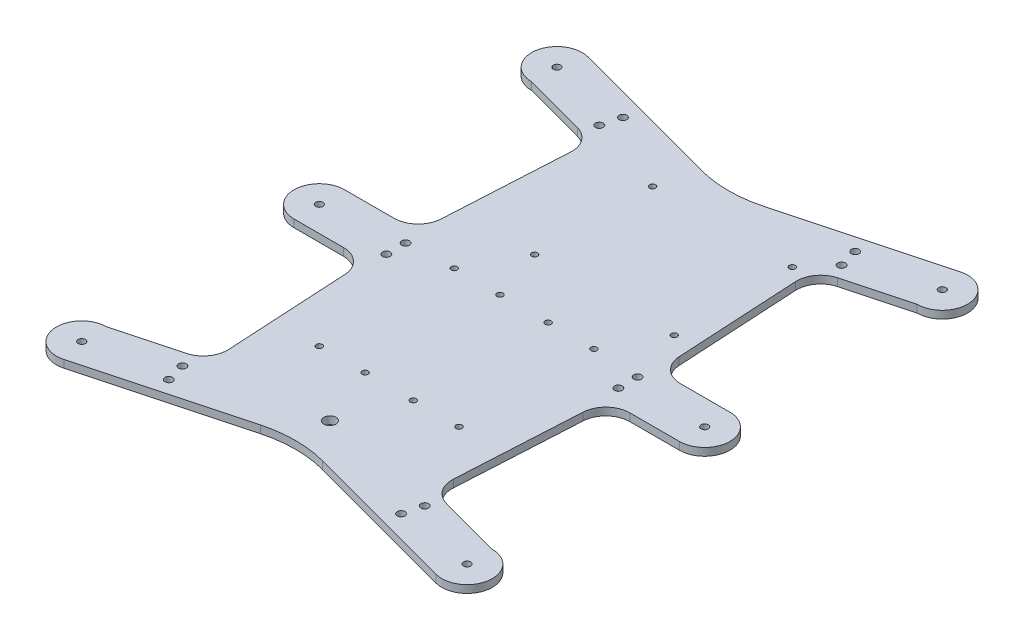
SolidWorks part; units mm, degrees
ref_plane "Front Plane" through (0, 0, 0) normal (0, 0, 1) x (1, 0, 0)
ref_plane "Top Plane" through (0, 0, 0) normal (0, 1, 0) x (1, 0, 0)
ref_plane "Right Plane" through (0, 0, 0) normal (1, 0, 0) x (0, 0, -1)
sketch "Sketch1" plane through (0, 0, 0) normal (0, 1, 0) x (1, 0, 0)
  line L0 (0, 32.1883) -> (0, -21.4181) construction
  line L1 (0, 0) -> (27.1703, 0) construction
  line L2 (-80, 10.5) -> (-50, 10.5)
  line L3 (-50, 10.5) -> (-46.1926, 79.0959)
  line L4 (-46.1926, 79.0959) -> (-80, 88.1546)
  line L5 (-77.2824, 108.7968) -> (0, 88.0891)
  line L6 (77.2824, 108.7968) -> (0, 88.0891)
  line L7 (46.1926, 79.0959) -> (80, 88.1546)
  line L8 (50, 10.5) -> (46.1926, 79.0959)
  line L9 (80, 10.5) -> (50, 10.5)
  line L10 (80, -10.5) -> (50, -10.5)
  line L11 (50, -10.5) -> (46.1926, -79.0959)
  line L12 (46.1926, -79.0959) -> (80, -88.1546)
  line L13 (77.2824, -108.7968) -> (0, -88.0891)
  line L14 (-77.2824, -108.7968) -> (0, -88.0891)
  line L15 (-46.1926, -79.0959) -> (-80, -88.1546)
  line L16 (-50, -10.5) -> (-46.1926, -79.0959)
  line L17 (-80, -10.5) -> (-50, -10.5)
  arc A0 (-80, 10.5) -> (-80, -10.5) centre (-80, 0) ccw
  arc A1 (-77.2824, 108.7968) -> (-80, 88.1546) centre (-80, 98.6546) ccw
  circle A2 centre (-80, 98.6546) radius 1.5
  circle A3 centre (-80, 0) radius 1.5
  circle A4 centre (80, 0) radius 1.5
  circle A5 centre (80, 98.6546) radius 1.5
  arc A6 (77.2824, 108.7968) -> (80, 88.1546) centre (80, 98.6546) cw
  arc A7 (80, 10.5) -> (80, -10.5) centre (80, 0) cw
  arc A8 (77.2824, -108.7968) -> (80, -88.1546) centre (80, -98.6546) ccw
  circle A9 centre (80, -98.6546) radius 1.5
  circle A10 centre (-80, -98.6546) radius 1.5
  arc A11 (-77.2824, -108.7968) -> (-80, -88.1546) centre (-80, -98.6546) cw
  circle A12 centre (-48.175, 4) radius 1.6 construction
  circle A13 centre (-50.2947, 86.554) radius 1.6 construction
  circle A14 centre (-48.2241, 94.2814) radius 1.6 construction
  circle A15 centre (-48.175, 4) radius 1.6
  circle A16 centre (-50.2947, 86.554) radius 1.6
  circle A17 centre (-48.2241, 94.2814) radius 1.6
  circle A18 centre (-50.2947, -86.554) radius 1.6
  circle A19 centre (-48.2241, -94.2814) radius 1.6
  circle A20 centre (-48.175, -4) radius 1.6
  circle A21 centre (48.2241, -94.2814) radius 1.6
  circle A22 centre (50.2947, -86.554) radius 1.6
  circle A23 centre (48.175, -4) radius 1.6
  circle A24 centre (48.175, 4) radius 1.6
  circle A25 centre (48.2241, 94.2814) radius 1.6
  circle A26 centre (50.2947, 86.554) radius 1.6
  dimension "D2" = 10.5
  dimension "D3" = 3
  dimension "D1" = 75
  dimension "D4" = 80
  dimension "D5" = 30
  dimension "D6" = 35
  dimension "D7" = 68.5959
extrude "Boss-Extrude1" add sketch "Sketch1" along normal blind 3.175
fillet "Fillet1" radius 50 2 edges at (0, 1.5875, -88.0891) (0, 1.5875, 88.0891)
fillet "Fillet2" radius 10 8 edges at (46.1926, 1.5875, 79.0959) (50, 1.5875, 10.5) (50, 1.5875, -10.5) (46.1926, 1.5875, -79.0959) (-46.1926, 1.5875, -79.0959) (-50, 1.5875, -10.5) (-50, 1.5875, 10.5) (-46.1926, 1.5875, 79.0959)
sketch "Sketch2" plane through (0, 3.175, 0) normal (0, 1, 0) x (1, 0, 0)
  line L0 (0, 89.8529) -> (0, -89.8529) construction
  line L1 (10, 5) -> (10, -51) construction
  line L2 (-17.25, 75.619) -> (40.75, 75.619) construction
  line L3 (-17.25, 75.619) -> (-17.25, 26.619) construction
  line L4 (-17.25, 26.619) -> (40.75, 26.619) construction
  line L5 (40.75, 75.619) -> (40.75, 26.619) construction
  line L6 (-17.25, 75.619) -> (-40.75, 75.619) construction
  line L7 (-17.25, 75.619) -> (-17.25, 26.619) construction
  line L8 (-17.25, 26.619) -> (-40.75, 26.619) construction
  line L9 (-40.75, 75.619) -> (-40.75, 26.619) construction
  line L10 (-29, 5) -> (-10, 5) construction
  line L11 (-29, 5) -> (-29, -51) construction
  line L12 (-29, -51) -> (-10, -51) construction
  line L13 (-10, 5) -> (-10, -51) construction
  line L14 (29, -51) -> (10, -51) construction
  line L15 (29, 5) -> (29, -51) construction
  line L16 (29, 5) -> (10, 5) construction
  arc A0 (-12.941, 91.5566) -> (12.941, 91.5566) centre (0, 139.8529) ccw construction
  arc A1 (12.941, -91.5566) -> (-12.941, -91.5566) centre (0, -139.8529) ccw construction
  circle A2 centre (-17.25, 75.619) radius 1.25
  circle A3 centre (40.75, 75.619) radius 1.25
  circle A4 centre (40.75, 26.619) radius 1.25
  circle A5 centre (-17.25, 26.619) radius 1.25
  circle A6 centre (0, -75.6029) radius 2.5
  circle A7 centre (-10, 5) radius 1.25
  circle A8 centre (-10, -51) radius 1.25
  circle A9 centre (-29, 5) radius 1.25
  circle A10 centre (-29, -51) radius 1.25
  circle A11 centre (29, -51) radius 1.25
  circle A12 centre (29, 5) radius 1.25
  circle A13 centre (10, -51) radius 1.25
  circle A14 centre (10, 5) radius 1.25
  dimension "D4" = 2.5
  dimension "D6" = 5
  dimension "D10" = 2.5
  dimension "D1" = 58
  dimension "D2" = 49
  dimension "D3" = 23.5
  dimension "D5" = 40.75
  dimension "D7" = 14.25
  dimension "D8" = 56
  dimension "D9" = 19
  dimension "D11" = 10
  dimension "D12" = 5
extrude "Cut-Extrude1" cut sketch "Sketch2" against normal through all both and the other way through all
